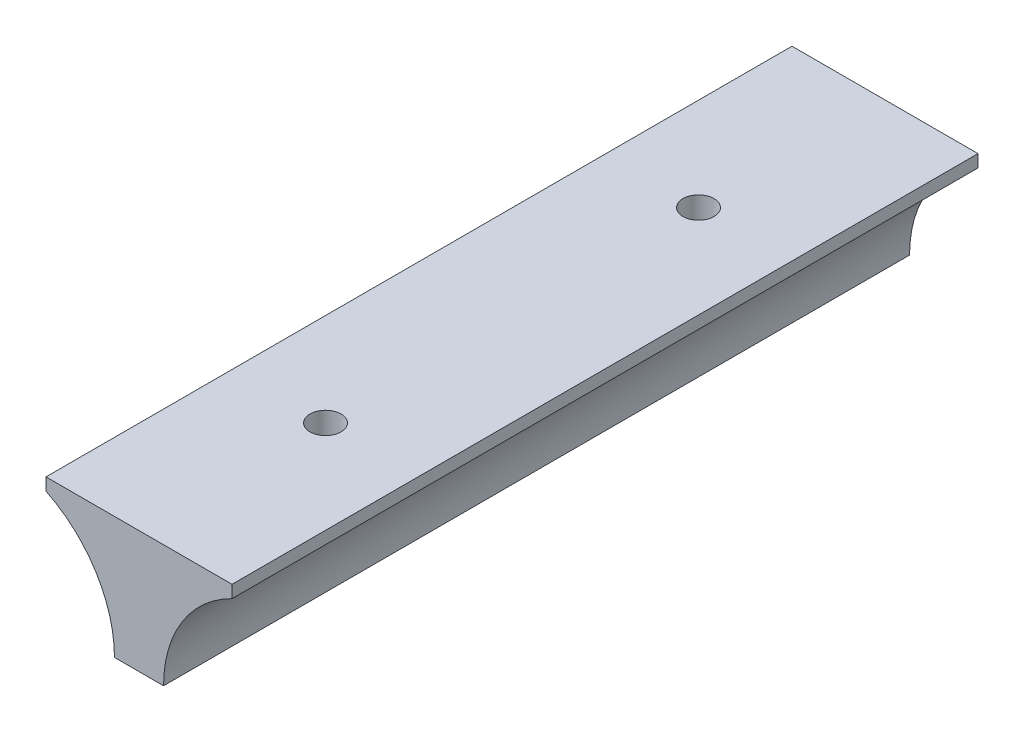
SolidWorks part; units mm, degrees
ref_plane "Front" through (0, 0, 0) normal (0, 0, 1) x (1, 0, 0)
ref_plane "Top" through (0, 0, 0) normal (0, 1, 0) x (1, 0, 0)
ref_plane "Right" through (0, 0, 0) normal (1, 0, 0) x (0, 0, -1)
sketch "Sketch1" plane through (0, 0, 0) normal (0, 0, 1) x (1, 0, 0)
  line L0 (-1.975, 0) -> (1.975, 0)
  line L1 (7.4814, 8.825) -> (7.4814, 9.825)
  line L2 (7.4814, 9.825) -> (-7.4814, 9.825)
  line L3 (-7.4814, 9.825) -> (-7.4814, 8.825)
  arc A0 (1.975, 0) -> (7.4814, 8.825) centre (11.8, 0) cw
  arc A1 (-1.975, 0) -> (-7.4814, 8.825) centre (-11.8, 0) ccw
  point P9 (0, 0)
  point P10 (0, 9.825)
  dimension "D1" = 9.825
  dimension "D2" = 9.825
  dimension "D3" = 3.95
  dimension "D4" = 1
extrude "Boss-Extrude1" add sketch "Sketch1" along normal blind 60
sketch "Sketch2" plane through (0, 9.825, 0) normal (0, 1, 0) x (1, 0, 0)
  line L0 (0, -60) -> (0, 0) construction
  line L1 (7.4814, -60) -> (-7.4814, -60) construction
  line L2 (7.4814, 0) -> (-7.4814, 0) construction
  point P6 (0, -45)
  point P7 (0, -15)
  dimension "D1" = 15
  dimension "D2" = 15
hole_wizard "Ø2.5 (2.5) Diameter Hole1" positions "3DSketch1" profile "Sketch3" hole size "Ø2.5" standard "ANSI Metric" end condition up to next
sketch3d "3DSketch1"
  point P0 (0, 9.825, 45)
  point P3 (0, 9.825, 15)
sketch "Sketch3" plane through (0, 9.825, 45) normal (1, 0, 0) x (0, 0, 1)
  line L0 (0, 0) -> (0, 9.825)
  line L1 (0, 9.825) -> (1.25, 9.825)
  line L2 (1.25, 9.825) -> (1.25, 0)
  line L5 (1.25, 0) -> (0, 0)
  line L11 (0, -6.35) -> (0, 107.95) construction
  dimension "Thru Hole Dia." = 2.5
  dimension "Thru Hole Depth" = 9.825
